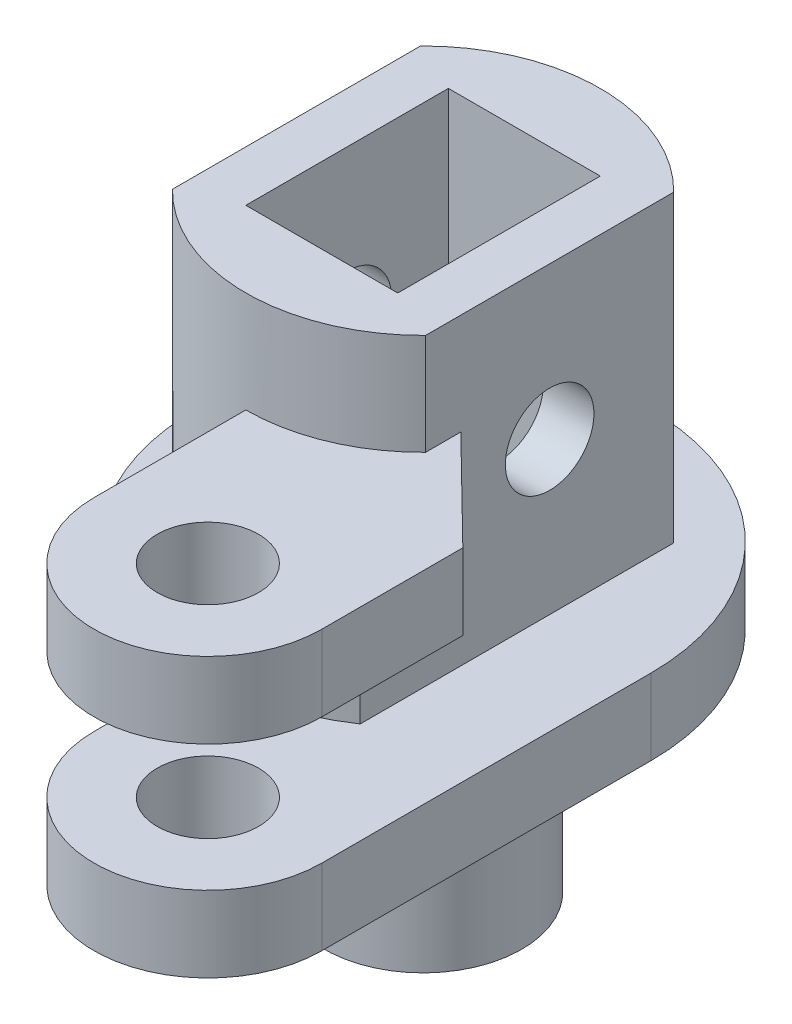
SolidWorks part; units mm, degrees
other "Markup1"
sketch "Sketch25" plane through (9, 15, 17.5) normal (0.6941, 0.3653, 0.6203) x (0.635, -0.7165, -0.2888)
ref_plane "Front Plane" through (0, 0, 0) normal (0, 0, 1) x (1, 0, 0)
ref_plane "Top Plane" through (0, 0, 0) normal (0, 1, 0) x (1, 0, 0)
ref_plane "Right Plane" through (0, 0, 0) normal (1, 0, 0) x (0, 0, -1)
sketch "Sketch1" plane through (0, 0, 0) normal (0, 1, 0) x (1, 0, 0)
  circle A0 centre (0, 0) radius 9
  dimension "D1" = 18
extrude "main body" add sketch "Sketch1" along normal blind 15
sketch "Sketch4" plane through (0, 0, 0) normal (0, -1, 0) x (1, 0, 0)
  circle A0 centre (0, 0) radius 6.4
  circle A1 centre (0, 0) radius 9 construction
  dimension "D1" = 12.8
extrude "Boss-Extrude3" add sketch "Sketch4" along normal blind 2 contours A0
sketch "Sketch5" plane through (0, -2, 0) normal (0, -1, 0) x (1, 0, 0)
  circle A0 centre (0, 0) radius 3.9
  circle A1 centre (0, 0) radius 6.4 construction
  dimension "D1" = 7.8
extrude "Boss-Extrude4" add sketch "Sketch5" along normal blind 7 contours A0
ref_plane "Plane1" through (0, 8, 0) normal (0, 1, 0) x (1, 0, 0)
sketch "Sketch9" plane through (0, 0, 0) normal (0, -1, 0) x (1, 0, 0)
  line L0 (0, 9) -> (0, 13)
  line L1 (9, 0) -> (9, 13)
  line L2 (0, 13) -> (9, 13) construction
  circle A0 centre (0, 0) radius 9 construction
  arc A2 (9, 0) -> (0, 9) centre (0, 0) ccw
  arc A3 (9, 13) -> (0, 13) centre (4.5, 13) ccw
  circle A4 centre (4.5, 13) radius 2
  dimension "D2" = 4.5
  dimension "D1" = 4
extrude "arm atttach" add sketch "Sketch9" against normal blind 3
ref_plane "Plane2" through (5, 0, 0) normal (1, 0, 0) x (0, 0, -1)
sketch "Sketch11" plane through (5, 0, 0) normal (1, 0, 0) x (0, 0, -1)
  line L0 (9, 0) -> (9, 15) construction
  line L1 (-9, 15) -> (9, 15)
  line L2 (-9, 15) -> (-9, 3)
  line L3 (-9, 3) -> (9, 3)
  line L4 (9, 15) -> (9, 3)
  dimension "D1" = 12
extrude "Cut-Extrude1" cut sketch "Sketch11" along normal blind 5
sketch "Sketch13" plane through (0, 8, 0) normal (0, 1, 0) x (1, 0, 0)
  line L0 (0, -13) -> (0, -9)
  line L1 (9, -13) -> (9, -7.4292)
  line L2 (9, -7.4292) -> (5, -3.5092)
  line L3 (5, -7.4833) -> (5, 7.4833) construction
  line L4 (5, -3.5092) -> (5, -7.4833)
  arc A0 (0, -13) -> (9, -13) centre (4.5, -13) ccw
  arc A1 (0, -9) -> (5, -7.4833) centre (0, 0) ccw
  circle A2 centre (4.5, -13) radius 2
extrude "arm attach" add sketch "Sketch13" along normal blind 3
ref_plane "Plane4" through (-5, 0, 0) normal (-1, 0, 0) x (0, 0, 1)
sketch "Sketch19" plane through (0, 15, 0) normal (0, 1, 0) x (1, 0, 0)
  line L0 (0, -7) -> (0, -9)
  line L1 (7.0839, -5.5514) -> (5.6441, -4.1405)
  line L2 (9, -7.4292) -> (5, -3.5092) construction
  arc A0 (5.6441, -4.1405) -> (0, -7) centre (0, 0) ccw
  arc A1 (7.0839, -5.5514) -> (0, -9) centre (0, 0) ccw
  dimension "D1" = 14
extrude "Cut-Extrude5" cut sketch "Sketch19" against normal up to surface (12 mm away) up to face at (4.8416, 3, 6.5616)
sketch "Sketch14" plane through (0, 15, 0) normal (0, 1, 0) x (1, 0, 0)
  line L1 (-3, 4) -> (3, 4)
  line L2 (-3, 4) -> (-3, -4)
  line L3 (-3, -4) -> (3, -4)
  line L4 (3, 4) -> (3, -4)
  line L5 (-3, 4) -> (3, -4) construction
  line L6 (-3, -4) -> (3, 4) construction
  point P0 (0, 0)
  dimension "D1" = 6
  dimension "D2" = 8
extrude "blade hole" cut sketch "Sketch14" against normal up to surface (12 mm away) up to face at (1.0369, 3, 5.4786)
sketch "Sketch21" plane through (-5, 0, 0) normal (-1, 0, 0) x (0, 0, 1)
  line L0 (-7, 9) -> (7, 9) construction
  line L1 (-7.5, 15) -> (7.5, 15)
  line L2 (-7.5, 15) -> (-7.5, 3)
  line L3 (-7.5, 3) -> (7.5, 3)
  line L4 (7.5, 15) -> (7.5, 3)
  line L5 (-7.5, 15) -> (7.5, 3) construction
  line L6 (-7.5, 3) -> (7.5, 15) construction
  line L7 (-7, 15) -> (-7, 3) construction
  line L8 (7, 3) -> (7, 15) construction
  point P0 (0, 9)
  dimension "D1" = 12
  dimension "D2" = 15
extrude "face cut" cut sketch "Sketch21" along normal blind 10
sketch "Sketch23" plane through (0, 15, 0) normal (0, 1, 0) x (1, 0, 0)
  circle A0 centre (0, 0) radius 7
  circle A1 centre (0, 0) radius 9
extrude "Cut-Extrude8" cut sketch "Sketch23" against normal up to surface (4 mm away) up to face at (4.6854, 11, 9.7154)
sketch "Sketch24" plane through (-5, 0, 0) normal (-1, 0, 0) x (0, 0, 1)
  line L0 (0, 15) -> (0, 3) construction
  line L1 (4.899, 15) -> (-4.899, 15) construction
  line L2 (9, 3) -> (-9, 3) construction
  circle A0 centre (0, 9) radius 1.75
  dimension "D1" = 3.5
extrude "screw hole" cut sketch "Sketch24" against normal mid plane 30
sketch "Sketch26" plane through (0, 0, 0) normal (0, 1, 0) x (1, 0, 0)
  circle A0 centre (0, 0) radius 1.65
  dimension "D1" = 3.3
extrude "Cut-Extrude9" cut sketch "Sketch26" against normal through all both and the other way through all
